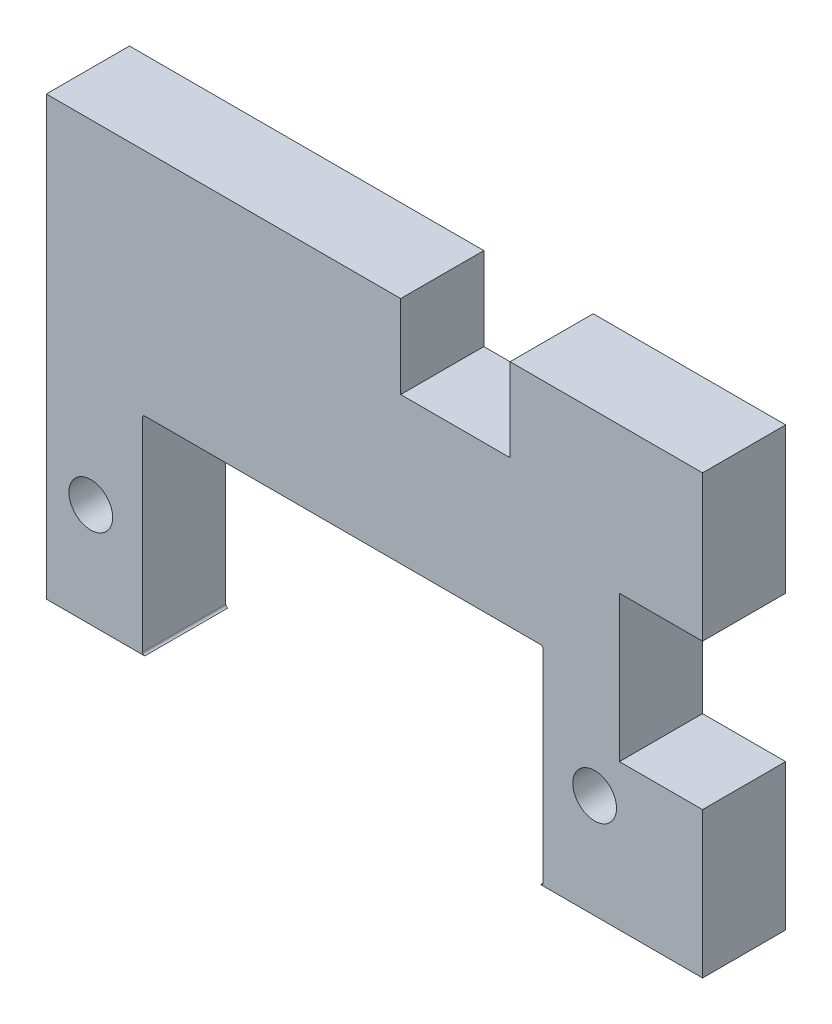
SolidWorks part; units mm, degrees
ref_plane "Front Plane" through (0, 0, 0) normal (0, 0, 1) x (1, 0, 0)
ref_plane "Top Plane" through (0, 0, 0) normal (0, 1, 0) x (1, 0, 0)
ref_plane "Right Plane" through (0, 0, 0) normal (1, 0, 0) x (0, 0, -1)
sketch "Sketch1" plane through (0, 0, 0) normal (0, 0, 1) x (1, 0, 0)
  line L1 (0, 0) -> (38.1, 0)
  line L2 (0, 0) -> (0, 25.4)
  line L3 (0, 25.4) -> (38.1, 25.4)
  line L4 (38.1, 0) -> (38.1, 25.4)
  dimension "D1" = 38.1
  dimension "D2" = 25.4
extrude "Boss-Extrude1" add sketch "Sketch1" along normal blind 4.826
sketch "Sketch2" plane through (0, 0, 4.826) normal (0, 0, 1) x (1, 0, 0)
  line L0 (38.1, 0) -> (38.1, 25.4) construction
  line L1 (38.1, 8.4667) -> (33.274, 8.4667)
  line L2 (38.1, 8.4667) -> (38.1, 16.9333)
  line L3 (38.1, 16.9333) -> (33.274, 16.9333)
  line L4 (33.274, 8.4667) -> (33.274, 16.9333)
  line L5 (33.274, 8.4667) -> (33.274, 0) construction
  line L6 (0, 0) -> (38.1, 0) construction
  line L7 (33.274, 16.9333) -> (33.274, 25.4) construction
  line L8 (38.1, 25.4) -> (0, 25.4) construction
  dimension "D1" = 4.826
extrude "Cut-Extrude1" cut sketch "Sketch2" against normal through all
sketch "Sketch3" plane through (0, 0, 4.826) normal (0, 0, 1) x (1, 0, 0)
  circle A2 centre (2.5805, 6.0325) radius 1.27
  circle A3 centre (31.8365, 6.0325) radius 1.27
extrude "Cut-Extrude2" cut sketch "Sketch3" against normal through all
sketch "Sketch4" plane through (0, 0, 0) normal (0, 0, -1) x (-1, 0, 0)
  line L0 (-28.702, 12.065) -> (-5.715, 12.065) construction
  line L1 (-28.829, 0.127) -> (-28.829, 11.938) construction
  line L2 (-5.588, 11.938) -> (-5.588, 0.127) construction
  line L3 (-5.715, 0) -> (-28.702, 0) construction
  line L4 (-28.702, 12.065) -> (-5.715, 12.065)
  line L5 (-28.829, 0.127) -> (-28.829, 11.938)
  line L6 (-5.588, 11.938) -> (-5.588, 0.127)
  line L7 (-5.715, 0) -> (-28.702, 0)
  arc A0 (-5.715, 0) -> (-5.588, 0.127) centre (-5.715, 0.127) ccw construction
  arc A1 (-28.829, 0.127) -> (-28.702, 0) centre (-28.702, 0.127) ccw construction
  arc A2 (-28.702, 12.065) -> (-28.829, 11.938) centre (-28.702, 11.938) ccw construction
  arc A3 (-5.588, 11.938) -> (-5.715, 12.065) centre (-5.715, 11.938) ccw construction
  arc A4 (-5.715, 0) -> (-5.588, 0.127) centre (-5.715, 0.127) ccw
  arc A5 (-28.829, 0.127) -> (-28.702, 0) centre (-28.702, 0.127) ccw
  arc A6 (-28.702, 12.065) -> (-28.829, 11.938) centre (-28.702, 11.938) ccw
  arc A7 (-5.588, 11.938) -> (-5.715, 12.065) centre (-5.715, 11.938) ccw
extrude "Cut-Extrude3" cut sketch "Sketch4" against normal through all
sketch "Sketch5" plane through (0, 0, 4.826) normal (0, 0, 1) x (1, 0, 0)
  line L0 (20.574, 20.574) -> (20.574, 25.4) construction
  line L1 (20.574, 20.574) -> (26.924, 20.574) construction
  line L2 (20.574, 20.574) -> (20.574, 25.4)
  line L3 (20.574, 20.574) -> (26.924, 20.574)
  line L4 (26.924, 20.574) -> (26.924, 25.4) construction
  line L5 (20.574, 25.4) -> (26.924, 25.4) construction
  line L6 (26.924, 20.574) -> (26.924, 25.4)
  line L7 (20.574, 25.4) -> (26.924, 25.4)
extrude "Cut-Extrude4" cut sketch "Sketch5" against normal through all
equation "\"MDF\"= 0.19in"
equation "\"PVCID\" = 2.067in"
equation "\"PVCOD\" = 2.375in"
equation "\"GenDiameter\"= 60mm"
equation "\"GenCutDiameter\" = 1.8in"
equation "\"GenCutDistance\" = 1"
equation "\"TowerHeight\" = 6in"
equation "\"TowerFrontBase\" = 3in"
equation "\"FunnelHeight\" = 1in"
equation "\"FunnelAngle\" = 20"
equation "\"TowerSideBase\" = 3in"
equation "\"TowerPanelLength\" = 2in"
equation "\"TowerPanelLeeway\" = 0.5in"
equation "\"BaseLength\" = 9in"
equation "\"BaseWidth\" = 10in"
equation "\"WheelHoleLength\" = 3.25in"
equation "\"WheelHoleWidth\" = 26mm"
equation "\"WheelHoleFromBack\" = 1.5in"
equation "\"DropLength\" = 1in"
equation "\"DropWidth\" = 8.5in"
equation "\"BumperWidth\" = 2in"
equation "\"SmallHexDiameter\" = 0.185in"
equation "\"SmallHexHeight\" = 0.701in"
equation "\"ScrewSize\" = 0.106in"
equation "\"BigHexDiameter\" = 0.251in"
equation "\"BigHexHeight\" = 0.374in"
equation "\"PCBThickness\" = 0.066in"
equation "\"ConnectorHeight\" = 0.517in"
equation "\"BoardHeight\" = 0.583in"
equation "\"UnoStackHeight\" = 1.351in"
equation "\"UnoStackWidth\" = 3.053in"
equation "\"UnoStackLength\" = 3.152in"
equation "\"HBridgeWidth\" = 1.797in"
equation "\"HBridgeLength\" = 2.236in"
equation "\"DSWidth\" = 1.820in"
equation "\"DSLength\" = 1.833in"
equation "\"StepperWidth\" = 1.799in"
equation "\"StepperLength\" = 2.248in"
equation "\"ULNWidth\" = 1.304in"
equation "\"ULNLength\" = 1.545in"
equation "\"VSwitchHeight\" = 0.392in"
equation "\"VSwitchWidth\" = 0.637in"
equation "\"VSwitchLength\" = 1.097in"
equation "\"SkateWheelDiameter\" = 80mm"
equation "\"SkateWheelThickness\" = 24mm"
equation "\"BaseDistance\" = 3in"
equation "\"DummyVar\" = 2in"
equation "\"D1@Boss-Extrude1\"=\"MDF\""
equation "\"D1@Sketch2\"=\"MDF\""
